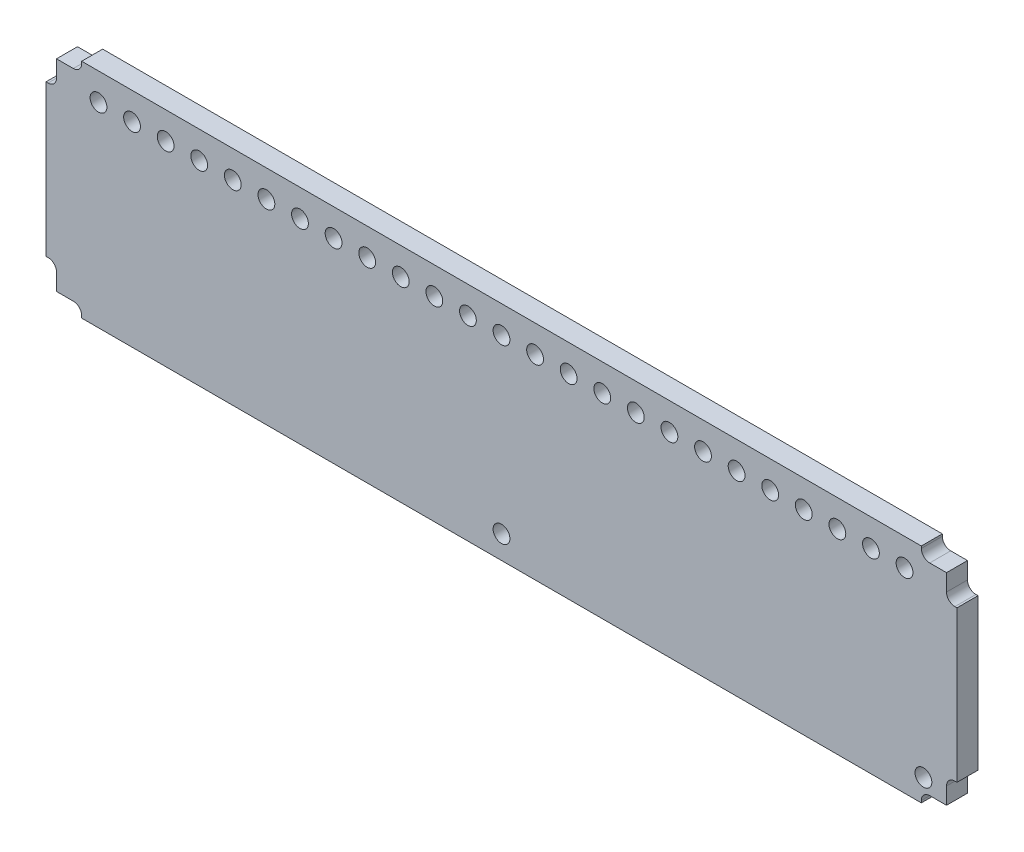
SolidWorks part; units mm, degrees
ref_plane "Front Plane" through (0, 0, 0) normal (0, 0, 1) x (1, 0, 0)
ref_plane "Top Plane" through (0, 0, 0) normal (0, 1, 0) x (1, 0, 0)
ref_plane "Right Plane" through (0, 0, 0) normal (1, 0, 0) x (0, 0, -1)
sketch "Sketch1" plane through (0, 0, 0) normal (0, 0, 1) x (1, 0, 0)
  line L1 (336.55, 76.2) -> (-336.55, 76.2)
  line L2 (336.55, 76.2) -> (336.55, -76.2)
  line L3 (336.55, -76.2) -> (-336.55, -76.2)
  line L4 (-336.55, 76.2) -> (-336.55, -76.2)
  line L5 (336.55, 76.2) -> (-336.55, -76.2) construction
  line L6 (336.55, -76.2) -> (-336.55, 76.2) construction
  point P0 (0, 0)
  dimension "D1" = 673.1
  dimension "D2" = 152.4
extrude "Boss-Extrude1" add sketch "Sketch1" along normal mid plane 15.875
sketch "Sketch2" plane through (0, 0, 7.9375) normal (0, 0, 1) x (1, 0, 0)
  line L0 (-336.55, 76.2) -> (-336.55, -76.2) construction
  line L1 (-336.55, 57.15) -> (-344.4875, 57.15)
  line L2 (-336.55, 57.15) -> (-336.55, -57.15)
  line L3 (-336.55, -57.15) -> (-344.4875, -57.15)
  line L4 (-344.4875, 57.15) -> (-344.4875, -57.15)
  line L5 (336.55, 76.2) -> (-336.55, 76.2) construction
  line L6 (-317.5, 76.2) -> (317.5, 76.2)
  line L7 (-317.5, 76.2) -> (-317.5, 84.1375)
  line L8 (-317.5, 84.1375) -> (317.5, 84.1375)
  line L9 (317.5, 76.2) -> (317.5, 84.1375)
  line L10 (-336.55, -76.2) -> (336.55, -76.2) construction
  line L11 (-317.5, -76.2) -> (317.5, -76.2)
  line L12 (-317.5, -76.2) -> (-317.5, -84.1375)
  line L13 (-317.5, -84.1375) -> (317.5, -84.1375)
  line L14 (317.5, -76.2) -> (317.5, -84.1375)
  line L15 (336.55, -76.2) -> (336.55, 76.2) construction
  line L16 (336.55, 57.15) -> (344.4875, 57.15)
  line L17 (336.55, 57.15) -> (336.55, -57.15)
  line L18 (336.55, -57.15) -> (344.4875, -57.15)
  line L19 (344.4875, 57.15) -> (344.4875, -57.15)
  line L20 (0, 0) -> (0, 76.2) construction
  line L21 (0, 0) -> (-336.55, 0) construction
  dimension "D1" = 19.05
  dimension "D2" = 19.05
  dimension "D3" = 7.9375
  dimension "D4" = 168.275
  dimension "D5" = 688.975
extrude "Boss-Extrude2" add sketch "Sketch2" against normal up to surface (15.875 mm away) up to face at (0, 0, -7.9375)
fillet "Fillet1" radius 6.35 8 edges at (336.55, 57.15, 0) (336.55, -57.15, 0) (317.5, -76.2, 0) (-317.5, -76.2, 0) (-317.5, 76.2, 0) (-336.55, -57.15, 0) (-336.55, 57.15, 0) (317.5, 76.2, 0)
sketch "Sketch3" plane through (0, 0, 7.9375) normal (0, 0, 1) x (1, 0, 0)
  line L0 (344.4875, -57.15) -> (344.4875, 57.15) construction
  line L2 (336.55, 76.2) -> (323.85, 76.2) construction
  circle A0 centre (0, -66.675) radius 6.35
  circle A2 centre (0, 63.5) radius 6.35
  circle A3 centre (25.4, 63.5) radius 6.35
  circle A4 centre (50.8, 63.5) radius 6.35
  circle A5 centre (76.2, 63.5) radius 6.35
  circle A6 centre (101.6, 63.5) radius 6.35
  circle A7 centre (127, 63.5) radius 6.35
  circle A8 centre (152.4, 63.5) radius 6.35
  circle A9 centre (177.8, 63.5) radius 6.35
  circle A10 centre (203.2, 63.5) radius 6.35
  circle A11 centre (228.6, 63.5) radius 6.35
  circle A12 centre (254, 63.5) radius 6.35
  circle A13 centre (279.4, 63.5) radius 6.35
  circle A14 centre (304.8, 63.5) radius 6.35
  circle A15 centre (-25.4, 63.5) radius 6.35
  circle A16 centre (-50.8, 63.5) radius 6.35
  circle A17 centre (-76.2, 63.5) radius 6.35
  circle A18 centre (-101.6, 63.5) radius 6.35
  circle A19 centre (-127, 63.5) radius 6.35
  circle A20 centre (-152.4, 63.5) radius 6.35
  circle A21 centre (-177.8, 63.5) radius 6.35
  circle A22 centre (-203.2, 63.5) radius 6.35
  circle A23 centre (-228.6, 63.5) radius 6.35
  circle A24 centre (-254, 63.5) radius 6.35
  circle A25 centre (-279.4, 63.5) radius 6.35
  circle A26 centre (-304.8, 63.5) radius 6.35
  circle A27 centre (319.0875, -66.675) radius 6.35
  point P5 (0, 0)
  dimension "D1" = 66.675
  dimension "D2" = 12.7
  dimension "D4" = 12.7
  dimension "D7" = 25.4
  dimension "D3" = 12.7
  dimension "D5" = 13
  dimension "D6" = 13
extrude "Cut-Extrude1" cut sketch "Sketch3" against normal through all both and the other way through all
